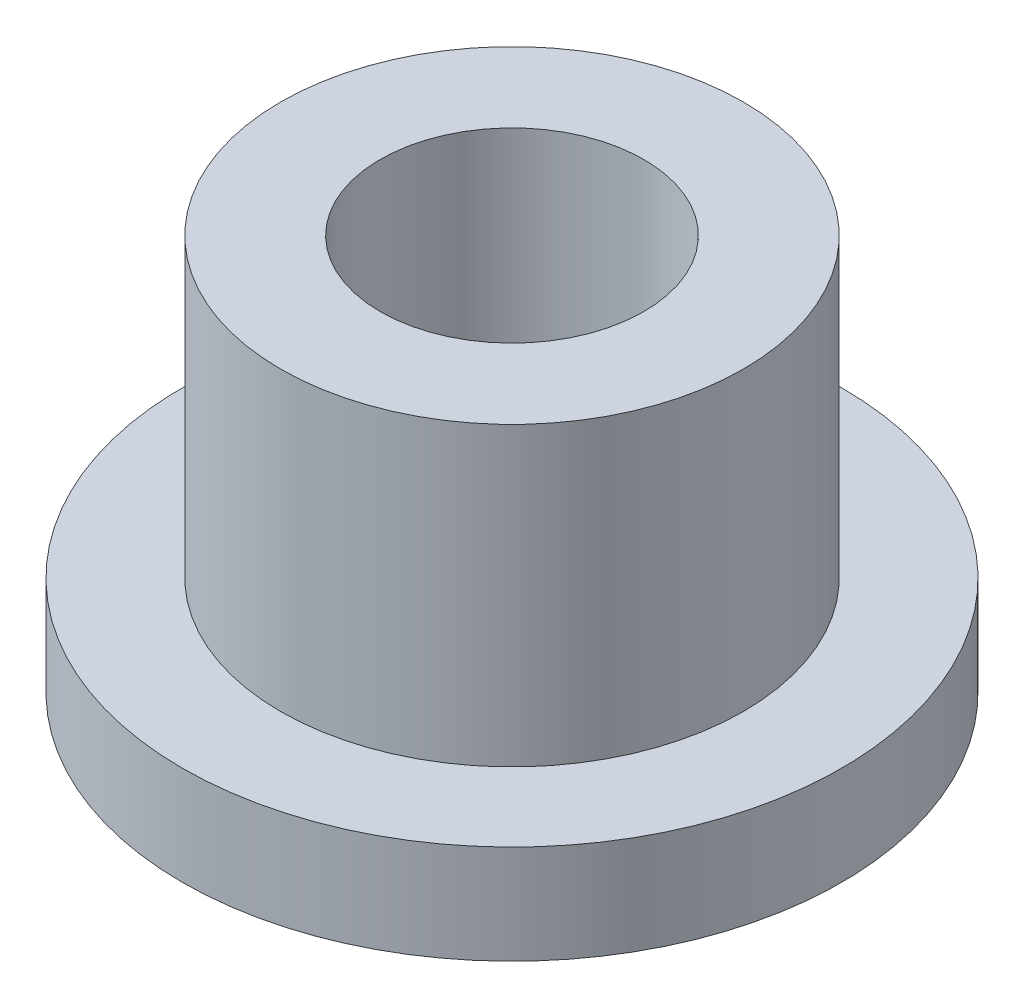
SolidWorks part; units mm, degrees
material "Commercial Bronze, UNS C22000 (90-10 Bronze)"
ref_plane "Front" through (0, 0, 0) normal (0, 0, 1) x (1, 0, 0)
ref_plane "Top" through (0, 0, 0) normal (0, 1, 0) x (1, 0, 0)
ref_plane "Right" through (0, 0, 0) normal (1, 0, 0) x (0, 0, -1)
sketch "Sketch1" plane through (0, 0, 0) normal (0, 1, 0) x (1, 0, 0)
  line L0 (0, 0) -> (0, 5) construction
  line L1 (0, 0) -> (0, -5) construction
  circle A0 centre (0, 0) radius 2
  circle A1 centre (0, 0) radius 3.51
  circle A2 centre (0, 0) radius 5
  point P7 (0, 5)
  point P9 (0, -5)
  dimension "ID" = 4
  dimension "OD" = 7.02
  dimension "FlangeOD" = 10
sketch "Sketch2" plane through (0, 0, 0) normal (1, 0, 0) x (0, 0, -1)
  line L0 (5, 0) -> (-5, 0) construction
  line L1 (5, 3) -> (0, 3)
  line L2 (5, 3) -> (5, -3)
  line L3 (5, -3) -> (0, -3)
  line L4 (0, 3) -> (0, -3)
  line L5 (5, -1.5) -> (0, -1.5) construction
  line L6 (0, -1.5) -> (-5, -1.5) construction
  line L7 (0, -3) -> (-5, -3) construction
  point P4 (0, 0)
  point P7 (5, 0)
  point P8 (0, -1.5)
  point P11 (5, -1.5)
  point P16 (-5, -1.5)
  point P19 (-5, -3)
  dimension "Overall Length" = 6
  dimension "Flange Thickness" = 1.5
sketch "Sketch5" plane through (0, 0, 0) normal (0, 1, 0) x (1, 0, 0)
  circle A0 centre (0, 0) radius 2 construction
  circle A1 centre (0, 0) radius 3.51 construction
  circle A2 centre (0, 0) radius 2
  circle A3 centre (0, 0) radius 3.51
extrude "Boss-Extrude1" add sketch "Sketch5" along normal up to vertex (3 mm away) and the other way up to vertex (3 mm away) up to point (0, 3, -5) other way up to point (0, -3, -5)
sketch "Sketch7" plane through (0, 0, 0) normal (0, 1, 0) x (1, 0, 0)
  circle A0 centre (0, 0) radius 3.51 construction
  circle A1 centre (0, 0) radius 5 construction
  circle A2 centre (0, 0) radius 3.51
  circle A3 centre (0, 0) radius 5
extrude "Boss-Extrude2" add sketch "Sketch7" along normal up to vertex (-1.5 mm away) from vertex up to point (0, -1.5, -5) starting at point (0, -3, -5)
ref_axis "Center Axis" through (0, 17.6, 0) along (0, -1, 0)
